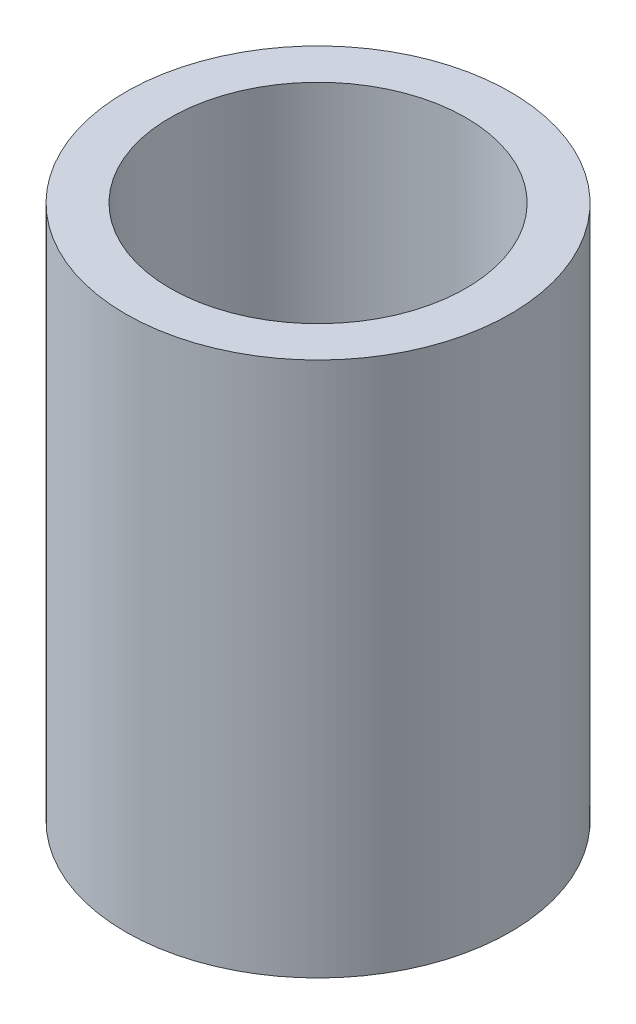
SolidWorks part; units mm, degrees
ref_plane "Front Plane" through (0, 0, 0) normal (0, 0, 1) x (1, 0, 0)
ref_plane "Top Plane" through (0, 0, 0) normal (0, 1, 0) x (1, 0, 0)
ref_plane "Right Plane" through (0, 0, 0) normal (1, 0, 0) x (0, 0, -1)
sketch "Sketch1" plane through (0, 0, 0) normal (0, 1, 0) x (1, 0, 0)
  circle A0 centre (0, 0) radius 35
  dimension "SLEEVE_OD" = 70
extrude "Boss-Extrude1" add sketch "Sketch1" along normal blind 97.381
sketch "Sketch2" plane through (0, 0, 0) normal (0, 1, 0) x (1, 0, 0)
  circle A0 centre (0, 0) radius 26.9036
  dimension "BORE_D" = 53.8072
extrude "Cut-Extrude1" cut sketch "Sketch2" along normal through all
chamfer "Chamfer1" distance 3.7135 angle 59.107 rebuild error yes
